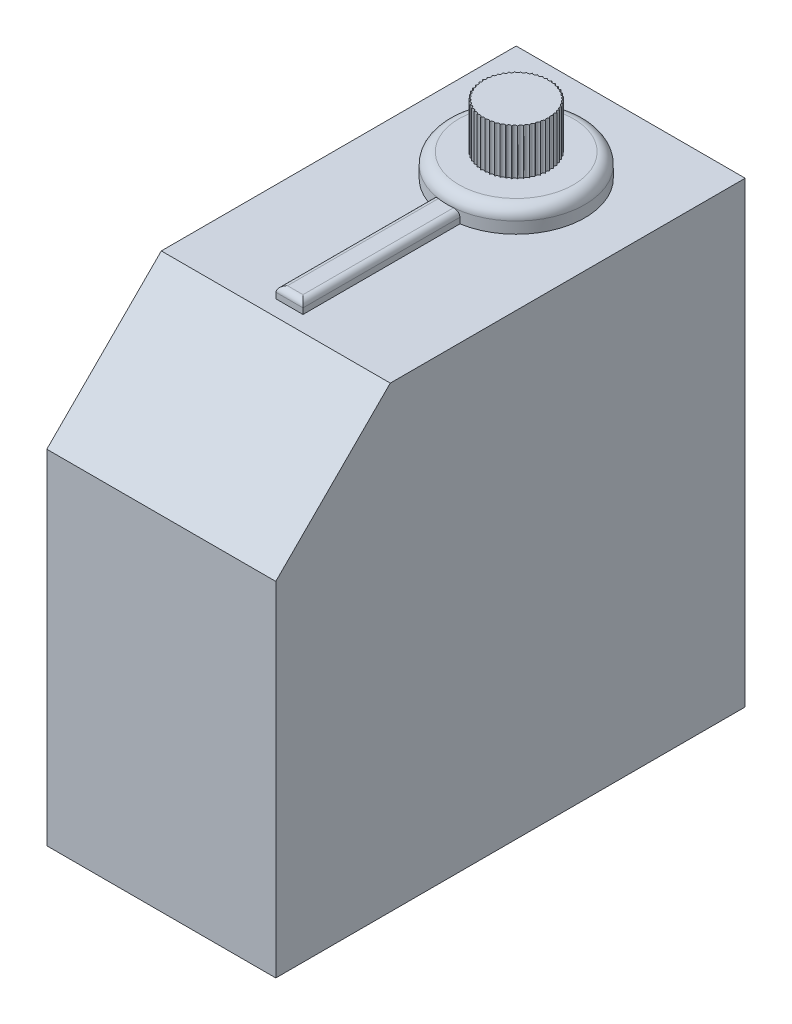
SolidWorks part; units mm, degrees
ref_plane "Front Plane" through (0, 0, 0) normal (0, 0, 1) x (1, 0, 0)
ref_plane "Top Plane" through (0, 0, 0) normal (0, 1, 0) x (1, 0, 0)
ref_plane "Right Plane" through (0, 0, 0) normal (1, 0, 0) x (0, 0, -1)
sketch "Sketch1" plane through (0, 0, 0) normal (0, 1, 0) x (1, 0, 0)
  line L1 (-10, 13.5809) -> (10, 13.5809)
  line L2 (-10, 13.5809) -> (-10, -27.4191)
  line L3 (-10, -27.4191) -> (10, -27.4191)
  line L4 (10, 13.5809) -> (10, -27.4191)
  dimension "D1" = 10
  dimension "D2" = 10
  dimension "D3" = 41
extrude "Boss-Extrude1" add sketch "Sketch1" along normal blind 40
chamfer "Chamfer1" distance 10 angle 45 1 edges at (0, 40, 27.4191)
sketch "Sketch2" plane through (0, 40, 0) normal (0, 1, 0) x (1, 0, 0)
  line L0 (-10, 13.5809) -> (-10, -17.4191) construction
  line L1 (10, 13.5809) -> (-10, 13.5809) construction
  circle A0 centre (0, 3.5809) radius 6
  dimension "D1" = 10
  dimension "D2" = 10
extrude "Boss-Extrude2" add sketch "Sketch2" along normal blind 2
fillet "Fillet1" radius 1 1 edges at (0, 42, 2.4191)
sketch "Sketch3" plane through (0, 40, 0) normal (0, 1, 0) x (1, 0, 0)
  line L1 (-1.3579, -0.7205) -> (0.9993, -0.7205)
  line L2 (-1.3579, -0.7205) -> (-1.3579, -16.0414)
  line L3 (-1.3579, -16.0414) -> (0.9993, -16.0414)
  line L4 (0.9993, -0.7205) -> (0.9993, -16.0414)
extrude "Boss-Extrude3" add sketch "Sketch3" along normal blind 1
fillet "Fillet2" radius 0.5 3 edges at (0.9993, 41, 9.1883) (-0.1793, 41, 16.0414) (-1.3579, 41, 9.1524)
sketch "Sketch4" plane through (0, 42, 0) normal (0, 1, 0) x (1, 0, 0)
  line L0 (10, 13.5809) -> (-10, 13.5809) construction
  line L1 (-10, 13.5809) -> (-10, -17.4191) construction
  circle A0 centre (0, 3.5809) radius 3
  dimension "D1" = 10
  dimension "D2" = 10
extrude "Boss-Extrude4" add sketch "Sketch4" along normal blind 4
sketch "Sketch5" plane through (0, 46, 0) normal (0, 1, 0) x (1, 0, 0)
  circle A0 centre (0, 0.5809) radius 0.2
  circle A1 centre (0, 3.5809) radius 3 construction
  circle A2 centre (-0.376, 0.6046) radius 0.2
  circle A3 centre (-0.7461, 0.6752) radius 0.2
  circle A4 centre (-1.1044, 0.7916) radius 0.2
  circle A5 centre (-1.4453, 0.952) radius 0.2
  circle A6 centre (-1.7634, 1.1539) radius 0.2
  circle A7 centre (-2.0536, 1.394) radius 0.2
  circle A8 centre (-2.3115, 1.6687) radius 0.2
  circle A9 centre (-2.533, 1.9735) radius 0.2
  circle A10 centre (-2.7145, 2.3036) radius 0.2
  circle A11 centre (-2.8532, 2.6539) radius 0.2
  circle A12 centre (-2.9469, 3.0188) radius 0.2
  circle A13 centre (-2.9941, 3.3926) radius 0.2
  circle A14 centre (-2.9941, 3.7693) radius 0.2
  circle A15 centre (-2.9469, 4.1431) radius 0.2
  circle A16 centre (-2.8532, 4.508) radius 0.2
  circle A17 centre (-2.7145, 4.8583) radius 0.2
  circle A18 centre (-2.533, 5.1884) radius 0.2
  circle A19 centre (-2.3115, 5.4932) radius 0.2
  circle A20 centre (-2.0536, 5.7679) radius 0.2
  circle A21 centre (-1.7634, 6.008) radius 0.2
  circle A22 centre (-1.4453, 6.2099) radius 0.2
  circle A23 centre (-1.1044, 6.3703) radius 0.2
  circle A24 centre (-0.7461, 6.4867) radius 0.2
  circle A25 centre (-0.376, 6.5573) radius 0.2
  circle A26 centre (0, 6.5809) radius 0.2
  circle A27 centre (0.376, 6.5573) radius 0.2
  circle A28 centre (0.7461, 6.4867) radius 0.2
  circle A29 centre (1.1044, 6.3703) radius 0.2
  circle A30 centre (1.4453, 6.2099) radius 0.2
  circle A31 centre (1.7634, 6.008) radius 0.2
  circle A32 centre (2.0536, 5.7679) radius 0.2
  circle A33 centre (2.3115, 5.4932) radius 0.2
  circle A34 centre (2.533, 5.1884) radius 0.2
  circle A35 centre (2.7145, 4.8583) radius 0.2
  circle A36 centre (2.8532, 4.508) radius 0.2
  circle A37 centre (2.9469, 4.1431) radius 0.2
  circle A38 centre (2.9941, 3.7693) radius 0.2
  circle A39 centre (2.9941, 3.3926) radius 0.2
  circle A40 centre (2.9469, 3.0188) radius 0.2
  circle A41 centre (2.8532, 2.6539) radius 0.2
  circle A42 centre (2.7145, 2.3036) radius 0.2
  circle A43 centre (2.533, 1.9735) radius 0.2
  circle A44 centre (2.3115, 1.6687) radius 0.2
  circle A45 centre (2.0536, 1.394) radius 0.2
  circle A46 centre (1.7634, 1.1539) radius 0.2
  circle A47 centre (1.4453, 0.952) radius 0.2
  circle A48 centre (1.1044, 0.7916) radius 0.2
  circle A49 centre (0.7461, 0.6752) radius 0.2
  circle A50 centre (0.376, 0.6046) radius 0.2
  point P104 (0, 3.5809)
  circle M2 centre (0, 3.5809) radius 3
  dimension "D1" = 50
extrude "Cut-Extrude1" cut sketch "Sketch5" against normal blind 4 contours A34 A33 A32 M2 | A34 A32 A33 M2 | A49 A47 A48 M2 | A49 A48 A47 M2 | A40 | A41 | A42 | A43 | A44 | A45 | A46 | A47 | A39 | A38 | A37 | A36 | A35 | A34 | A32 | A31 | A30 | A29 | A28 | A27 | A26 | A25 | A24 | A23 | A22 | A21 | A20 | A19 | A18 | A17 | A16 | A15 | A14 | A13 | A12 | A11 | A10 | A9 | A8 | A7 | A6 | A5 | A4 | A3 | A2 | A0 | A50 | A49 region at (1.1359, 46, -0.712) region at (1.0719, 46, -0.8736) region at (2.2436, 46, -5.437) region at (2.3775, 46, -5.5478)
